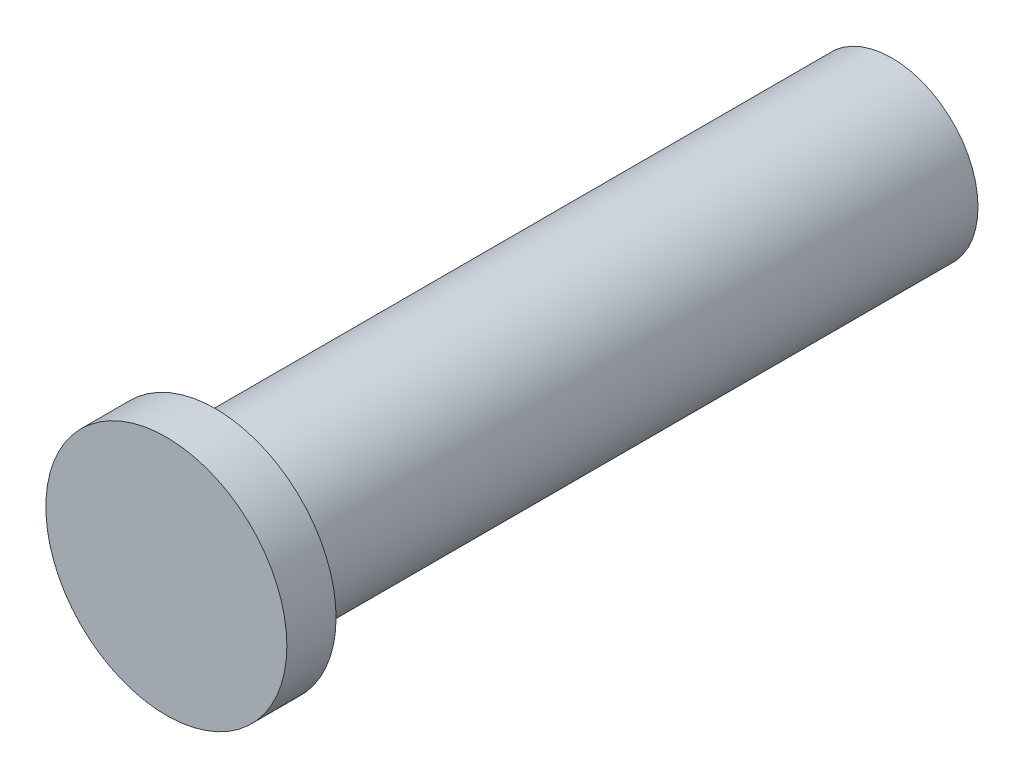
SolidWorks part; units mm, degrees
ref_plane "Front Plane" through (0, 0, 0) normal (0, 0, 1) x (1, 0, 0)
ref_plane "Top Plane" through (0, 0, 0) normal (0, 1, 0) x (1, 0, 0)
ref_plane "Right Plane" through (0, 0, 0) normal (1, 0, 0) x (0, 0, -1)
sketch "Sketch1" plane through (0, 0, 0) normal (0, 0, 1) x (1, 0, 0)
  circle A0 centre (0, 0) radius 7
  dimension "D1" = 14
extrude "Boss-Extrude1" add sketch "Sketch1" along normal blind 63
sketch "Sketch2" plane through (0, 0, 63) normal (0, 0, 1) x (1, 0, 0)
  circle A0 centre (0, 0) radius 9.8
  dimension "D1" = 19.6
extrude "Boss-Extrude2" add sketch "Sketch2" against normal blind 4
sketch "Sketch7" plane through (0, 0, 0) normal (0, 0, -1) x (-1, 0, 0)
  circle A0 centre (0, 0) radius 7
  circle A1 centre (0, 0) radius 7 construction
extrude "Cut-Extrude2" cut sketch "Sketch7" against normal blind 4
sketch "Sketch3" plane through (0, 0, 4) normal (0, 0, -1) x (-1, 0, 0)
  circle A0 centre (0, 0) radius 4.2
  dimension "D1" = 8.4
extrude "Cut-Extrude1" cut sketch "Sketch3" against normal blind 15
thread "Thread1" pitch 1 method cut profile "Thread Profile1" start angle 0, offset 0, length 0, pitch 1, diameter 8.4
ref_plane "Plane2" through (-4.2, 0, 19) normal (0, -1, 0) x (-1, 0, 0)
sketch "Thread Profile1" plane through (-4.2, 0, 19) normal (0, -1, 0) x (-1, 0, 0)
  line L0 (0, 0) -> (0, 1) construction
  line L1 (0, 0) -> (0.5413, 0.3125)
  line L2 (0.5413, 0.3125) -> (0.5413, 0.4375)
  line L3 (0.5413, 0.4375) -> (0, 0.75)
  line L4 (0.5413, 0.375) -> (0, 0.375) construction
  line L11 (0, 0) -> (0, 0.75)
  point P2 (0, 0)
  dimension "Pitch" = 1
  dimension "Profile_Angle" = 60
  dimension "Profile_Land" = 0.125
  dimension "Profile_Height" = 0.5413
equation "\"pin_diameter\"=14.00"
equation "\"upper_pin_length\"=63.00"
equation "\"lower_pin_length\"=33.00"
equation "\"D1@Sketch1\"=\"pin_diameter\""
equation "\"D1@Boss-Extrude1\"=\"upper_pin_length\""
equation "\"pin_head_diameter\"=19.60"
equation "\"D1@Sketch2\"=\"pin_head_diameter\""
equation "\"pin_screw_diameter\"=8.40"
equation "\"D1@Sketch3\"=\"pin_screw_diameter\""
